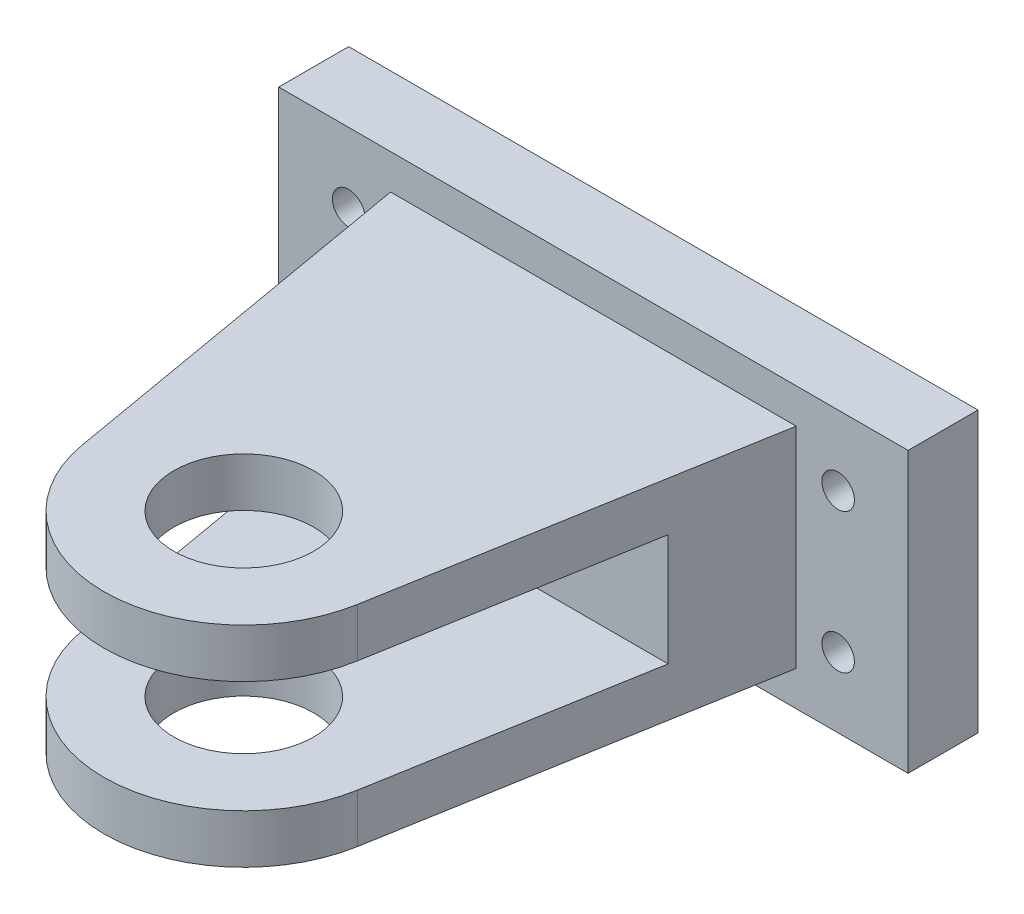
SolidWorks part; units mm, degrees
material "6061-T6 (SS)"
ref_plane "XY" through (0, 0, 0) normal (0, 0, 1) x (1, 0, 0)
ref_plane "XZ" through (0, 0, 0) normal (0, 1, 0) x (1, 0, 0)
ref_plane "YZ" through (0, 0, 0) normal (1, 0, 0) x (0, 0, -1)
ref_axis "X" through (-31.4325, 0, 0) along (1, 0, 0)
ref_axis "Y" through (0, -13.97, 0) along (0, 1, 0)
ref_axis "Z" through (0, 0, 53.34) along (0, 0, -1)
sketch "Sketch1" plane through (0, 0, 0) normal (0, 0, 1) x (1, 0, 0)
  line L1 (-28.575, -12.7) -> (28.575, -12.7)
  line L2 (-28.575, -12.7) -> (-28.575, 12.7)
  line L3 (-28.575, 12.7) -> (28.575, 12.7)
  line L4 (28.575, -12.7) -> (28.575, 12.7)
  line L5 (-28.575, -12.7) -> (28.575, 12.7) construction
  line L6 (-28.575, 12.7) -> (28.575, -12.7) construction
  point P0 (0, 0)
  dimension "D1" = 25.4
  dimension "D2" = 57.15
extrude "Boss-Extrude1" add sketch "Sketch1" along normal blind 6.35
hole_wizard "#4 Clearance Hole1" positions "Sketch2" profile "Sketch3" hole size "#4" standard "ANSI Inch" end condition up to next
sketch "Sketch2" plane through (0, 0, 6.35) normal (0, 0, 1) x (1, 0, 0)
  line L1 (-22.225, 6.35) -> (22.225, 6.35)
  line L2 (-22.225, 6.35) -> (-22.225, -6.35)
  line L3 (-22.225, -6.35) -> (22.225, -6.35)
  line L4 (22.225, 6.35) -> (22.225, -6.35)
  line L5 (0, -6.35) -> (0, 6.35) construction
  point P0 (-22.225, 6.35)
  point P5 (22.225, -6.35)
  point P108 (-22.225, -6.35)
  point P109 (22.225, 6.35)
  dimension "D1" = 12.7
  dimension "D2" = 44.45
sketch "Sketch3" plane through (-22.225, 6.35, 6.35) normal (1, 0, 0) x (0, -1, 0)
  line L0 (0, 0) -> (0, 6.35)
  line L1 (0, 6.35) -> (1.4732, 6.35)
  line L2 (1.4732, 6.35) -> (1.4732, 0)
  line L5 (1.4732, 0) -> (0, 0)
  line L11 (0, -6.35) -> (0, 107.95) construction
  dimension "Thru Hole Dia." = 2.9464
  dimension "Thru Hole Depth" = 6.35
sketch "Sketch4" plane through (0, 0, 0) normal (0, 1, 0) x (1, 0, 0)
  line L0 (0, 0) -> (0, -38.1) construction
  line L1 (-12.512, -40.277) -> (-18.415, -6.35)
  line L2 (-28.575, -6.35) -> (28.575, -6.35) construction
  line L3 (12.512, -40.277) -> (18.415, -6.35)
  line L4 (-18.415, -6.35) -> (18.415, -6.35)
  line L5 (28.575, 0) -> (-28.575, 0) construction
  circle A0 centre (0, -38.1) radius 12.7 construction
  circle A1 centre (0, -38.1) radius 6.35
  arc A2 (-12.512, -40.277) -> (12.512, -40.277) centre (0, -38.1) ccw
  point P3 (19.5195, -6.35)
  dimension "D1" = 25.4
  dimension "D3" = 12.7
  dimension "D4" = 25.4
  dimension "D2" = 38.1
  dimension "D5" = 36.83
extrude "Boss-Extrude2" add sketch "Sketch4" along normal mid plane 19.05
sketch "Sketch5" plane through (0, 0, 0) normal (0, 1, 0) x (1, 0, 0)
  line L0 (17.6416, -10.795) -> (-17.6416, -10.795)
  line L3 (12.512, -40.277) -> (18.415, -6.35)
  line L4 (18.415, -6.35) -> (-18.415, -6.35)
  line L5 (-18.415, -6.35) -> (-12.512, -40.277)
  line L6 (12.512, -40.277) -> (17.6416, -10.795)
  line L8 (-17.6416, -10.795) -> (-12.512, -40.277)
  circle A0 centre (0, -38.1) radius 6.35 construction
  arc A1 (-12.512, -40.277) -> (12.512, -40.277) centre (0, -38.1) ccw
  arc A2 (-12.512, -40.277) -> (12.512, -40.277) centre (0, -38.1) ccw
  circle A3 centre (0, -38.1) radius 6.35
  dimension "D2" = 27.305
  dimension "D1" = 0
extrude "Boss-Extrude3" add sketch "Sketch5" along normal mid plane 19.05
sketch "Sketch6" plane through (0, 0, 0) normal (0, 1, 0) x (1, 0, 0)
  line L0 (-16.6914, -16.256) -> (16.6914, -16.256)
  line L1 (-18.415, -6.35) -> (-12.512, -40.277) construction
  line L2 (12.512, -40.277) -> (18.415, -6.35) construction
  line L6 (-16.6914, -16.256) -> (-12.512, -40.277)
  line L8 (12.512, -40.277) -> (16.6914, -16.256)
  arc A0 (-12.512, -40.277) -> (12.512, -40.277) centre (0, -38.1) ccw construction
  arc A2 (-12.512, -40.277) -> (12.512, -40.277) centre (0, -38.1) ccw
  point P7 (-12.5131, -40.277)
  point P9 (0, 0)
  point P10 (-17.0462, -16.256)
  point P13 (0, 0)
  point P17 (0, 0)
  point P18 (0, 0)
  dimension "D1" = 21.844
extrude "Cut-Extrude1" cut sketch "Sketch6" against normal mid plane 10.16
